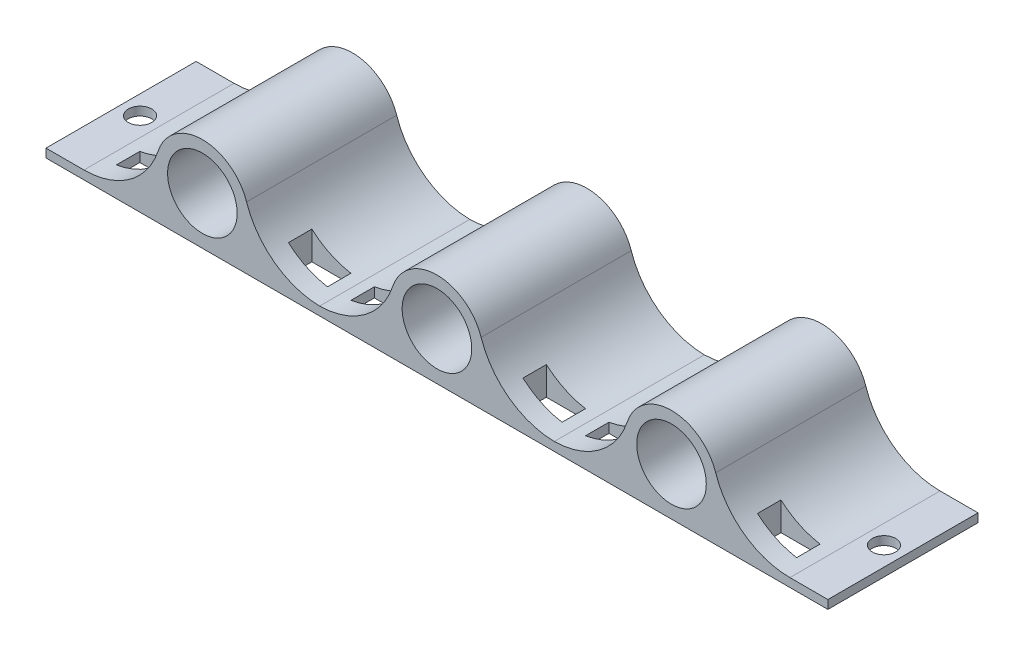
SolidWorks part; units mm, degrees
ref_plane "Plan de face" through (0, 0, 0) normal (0, 0, 1) x (1, 0, 0)
ref_plane "Plan de dessus" through (0, 0, 0) normal (0, 1, 0) x (1, 0, 0)
ref_plane "Plan de droite" through (0, 0, 0) normal (1, 0, 0) x (0, 0, -1)
sketch "Esquisse1" plane through (0, 0, 0) normal (0, 0, 1) x (1, 0, 0)
  circle A0 centre (0, 0) radius 4.45
  circle A1 centre (30, 0) radius 4.45
  circle A2 centre (60, 0) radius 4.45
  dimension "D1" = 8.9
  dimension "D3" = 30
  dimension "D2" = 3
extrude "Extru.-Mince1" add sketch "Esquisse1" along normal blind 19.2 thin
ref_plane "Plan1" through (0, -5, 0) normal (0, 1, 0) x (1, 0, 0)
sketch "Esquisse3" plane through (0, -5, 0) normal (0, 1, 0) x (1, 0, 0)
  line L0 (0, 0) -> (0, 22.3157) construction
  line L1 (-20, 0) -> (20, 0)
  line L2 (-20, 0) -> (-20, -19.2)
  line L3 (-20, -19.2) -> (20, -19.2)
  line L4 (0, 0) -> (0, -19.2)
  line L5 (24.05, 0) -> (35.95, -19.2) construction
  line L6 (24.05, 0) -> (35.95, 0) construction
  line L7 (-5.95, -19.2) -> (5.95, -19.2) construction
  line L8 (5.95, 0) -> (-5.95, 0) construction
  line L9 (20, 0) -> (20, -19.2)
  line L10 (24.05, 0) -> (24.05, -19.2) construction
  line L11 (24.05, -19.2) -> (35.95, -19.2) construction
  line L12 (35.95, 0) -> (35.95, -19.2) construction
  line L13 (54.05, 0) -> (65.95, 0) construction
  line L14 (54.05, 0) -> (54.05, -19.2) construction
  line L15 (54.05, -19.2) -> (65.95, -19.2) construction
  line L16 (65.95, 0) -> (65.95, -19.2) construction
  line L17 (54.05, 0) -> (65.95, -19.2) construction
  line L18 (20, 0) -> (40, -19.2) construction
  line L19 (20, 0) -> (40, 0)
  line L20 (20, 0) -> (20, -19.2)
  line L21 (20, -19.2) -> (40, -19.2)
  line L22 (40, 0) -> (40, -19.2)
  line L23 (40, 0) -> (80, 0)
  line L24 (40, 0) -> (40, -19.2)
  line L25 (40, -19.2) -> (80, -19.2)
  line L26 (80, 0) -> (80, -19.2)
  line L27 (40, 0) -> (80, -19.2) construction
  point P26 (60, -9.6)
  point P30 (30, -9.6)
  dimension "D1" = 20
extrude "Boss.-Extru.1" add sketch "Esquisse3" against normal blind 1.1 contours L4 L1 L2 L3 | L9 L1 L4 L3 | L20 L19 L22 L21 | L24 L23 L26 L25
fillet "Congé1" radius 10 4 edges at (3.2253, -5, 9.6) (56.7747, -5, 9.6) (33.2253, -5, 9.6) (26.7747, -5, 9.6)
sketch "Esquisse4" plane through (0, -5, 0) normal (0, 1, 0) x (1, 0, 0)
  line L0 (0, 9.5182) -> (0, -32.3497) construction
  line L1 (-13.5, -13.7) -> (-8.5, -13.7)
  line L2 (-13.5, -13.7) -> (-13.5, -16.7)
  line L3 (-13.5, -16.7) -> (-8.5, -16.7)
  line L4 (-8.5, -13.7) -> (-8.5, -16.7)
  line L5 (8.5, -13.7) -> (8.5, -16.7)
  line L6 (13.5, -16.7) -> (8.5, -16.7)
  line L7 (13.5, -13.7) -> (13.5, -16.7)
  line L8 (13.5, -13.7) -> (8.5, -13.7)
  line L9 (-20, -19.2) -> (80, -19.2) construction
  line L10 (16.5, -13.7) -> (16.5, -16.7)
  line L11 (16.5, -13.7) -> (21.5, -13.7)
  line L12 (21.5, -13.7) -> (21.5, -16.7)
  line L13 (16.5, -16.7) -> (21.5, -16.7)
  line L14 (38.5, -13.7) -> (38.5, -16.7)
  line L15 (43.5, -16.7) -> (38.5, -16.7)
  line L16 (43.5, -13.7) -> (43.5, -16.7)
  line L17 (43.5, -13.7) -> (38.5, -13.7)
  line L18 (46.5, -13.7) -> (46.5, -16.7)
  line L19 (46.5, -13.7) -> (51.5, -13.7)
  line L20 (51.5, -13.7) -> (51.5, -16.7)
  line L21 (46.5, -16.7) -> (51.5, -16.7)
  line L22 (68.5, -13.7) -> (68.5, -16.7)
  line L23 (73.5, -16.7) -> (68.5, -16.7)
  line L24 (73.5, -13.7) -> (73.5, -16.7)
  line L25 (73.5, -13.7) -> (68.5, -13.7)
  dimension "D1" = 5
  dimension "D2" = 3
  dimension "D3" = 8.5
  dimension "D4" = 2.5
  dimension "D6" = 3
  dimension "D5" = 3
extrude "Enlèv. mat.-Extru.1" cut sketch "Esquisse4" along normal through all both and the other way through all
sketch "Esquisse5" plane through (0, -5, 0) normal (0, 1, 0) x (1, 0, 0)
  line L0 (75.146, 0) -> (80, -19.2) construction
  line L1 (-20, 0) -> (-15.146, -19.2) construction
  line L2 (-20, 0) -> (-20, -19.2) construction
  line L3 (-20, 0) -> (-15.146, 0) construction
  line L4 (-15.146, -19.2) -> (-15.146, 0) construction
  line L5 (-15.146, -19.2) -> (-5.6501, -19.2) construction
  circle A0 centre (77.573, -9.6) radius 1.5
  circle A1 centre (-17.573, -9.6) radius 1.5
  point P10 (-17.3502, -9.6)
  point P11 (-20, 0)
  point P16 (-15.146, -19.2)
  dimension "D1" = 3
extrude "Enlèv. mat.-Extru.4" cut sketch "Esquisse5" against normal through all contours A0 L0 | L0 A0 | A1
